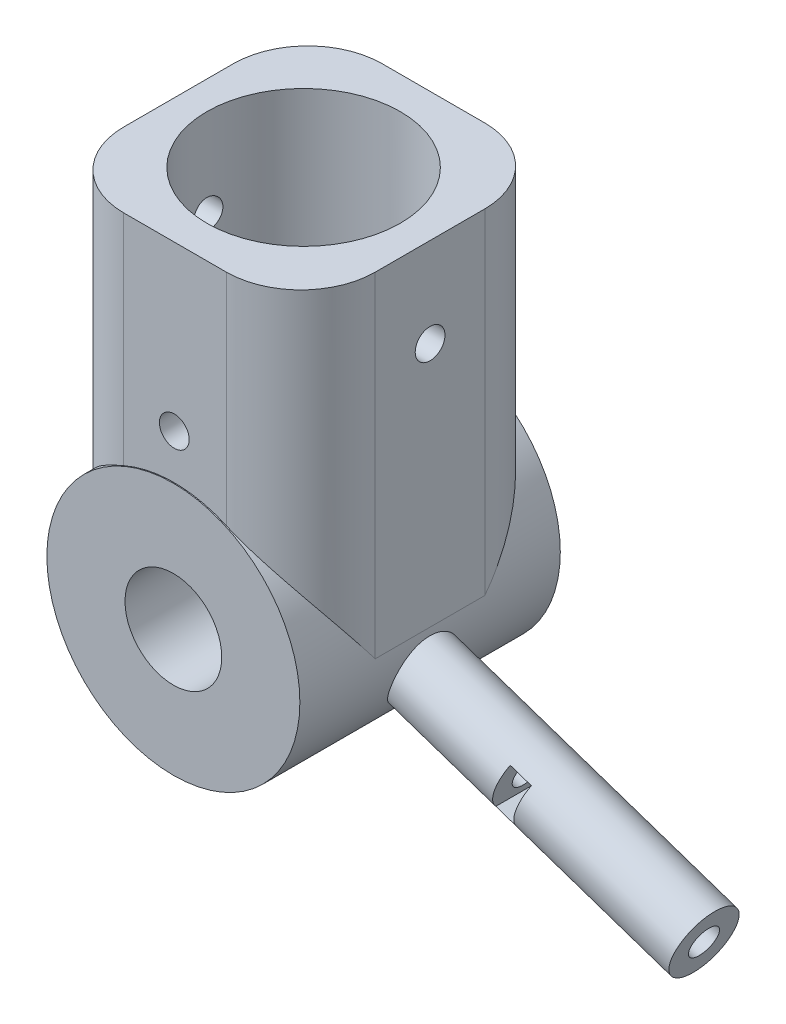
SolidWorks part; units mm, degrees
ref_plane "Спереди" through (0, 0, 0) normal (0, 0, 1) x (1, 0, 0)
ref_plane "Сверху" through (0, 0, 0) normal (0, 1, 0) x (1, 0, 0)
ref_plane "Справа" through (0, 0, 0) normal (1, 0, 0) x (0, 0, -1)
sketch "Эскиз1" plane through (0, 0, 0) normal (0, 0, 1) x (1, 0, 0)
  circle A0 centre (0, 0) radius 6.5
  circle A1 centre (0, 0) radius 17
extrude "Бобышка-Вытянуть2" add sketch "Эскиз1" along normal blind 35
ref_plane "Плоскость4" through (0, 45, 0) normal (0, 1, 0) x (1, 0, 0)
sketch "Эскиз3" plane through (0, 45, 0) normal (0, 1, 0) x (1, 0, 0)
  line L0 (17, -35) -> (17, 0) construction
  line L13 (-16.7953, -0.1471) -> (17, -0.1471)
  line L14 (-16.7953, -0.1471) -> (-16.7953, -34.8751)
  line L15 (-16.7953, -34.8751) -> (17, -34.8751)
  line L16 (17, -0.1471) -> (17, -34.8751)
  line L17 (-16.7953, -0.1471) -> (-17, 0) construction
  line L18 (-17, 0) -> (-17, -35) construction
  line L19 (-16.7953, -34.8751) -> (-17, -35) construction
  circle A1 centre (0, -17.5) radius 13
extrude "Бобышка-Вытянуть7" add sketch "Эскиз3" against normal blind 45
sketch "Эскиз4" plane through (0, 0, 0) normal (0, 0, -1) x (-1, 0, 0)
  circle A0 centre (0, 0) radius 6.5
extrude "Вырез-Вытянуть1" cut sketch "Эскиз4" against normal through all
sketch "Эскиз12" plane through (0, 0, 0) normal (0, 0, -1) x (-1, 0, 0)
  line L0 (0, 23) -> (0, 0) construction
  circle A3 centre (0, 23) radius 2
extrude "Вырез-Вытянуть11" cut sketch "Эскиз12" against normal blind 45
sketch "Эскиз15" plane through (-16.7953, 0, 0) normal (-1, 0, 0) x (0, 0, 1)
  line L0 (0, 0) -> (0, 33) construction
  line L1 (0, 33) -> (17.5, 33) construction
  circle A1 centre (17.5, 33) radius 2
extrude "Вырез-Вытянуть12" cut sketch "Эскиз15" against normal blind 45
fillet "Скругление4" radius 10 4 edges at (-16.7953, 23.8152, 0.1471) (17, 22.5, 0.1471) (17, 22.5, 34.8751) (-16.7953, 23.8152, 34.8751)
sketch "Эскиз20" plane through (0, 45, 0) normal (0, 1, 0) x (1, 0, 0)
  circle A3 centre (0, -17.5) radius 13
extrude "Вырез-Вытянуть18" cut sketch "Эскиз20" against normal blind 31
sketch "Эскиз25" plane through (0, 14, 0) normal (0, 1, 0) x (1, 0, 0)
  circle A2 centre (0, -17.5) radius 13
extrude "Бобышка-Вытянуть10" add sketch "Эскиз25" along normal blind 1
sketch3d "Трехмерный эскиз1"
  point P0 (-14.7779, 8.4033, 37.4657)
sketch "Эскиз26" plane through (0, 0, 0) normal (0, 0, -1) x (-1, 0, 0)
  circle A0 centre (0, 0) radius 6.5
  circle A1 centre (0, 0) radius 5.5
extrude "Бобышка-Вытянуть11" add sketch "Эскиз26" against normal blind 2
sketch3d "Трехмерный эскиз4"
  point P0 (0.8909, -16.9766, 11.3566)
sketch3d "Трехмерный эскиз5"
  point P0 (15.2365, -7.5398, 9.0171)
sketch3d "Трехмерный эскиз6"
  point P0 (16.5585, -3.8494, 24.0123)
sketch3d "Трехмерный эскиз7"
  point P0 (15.9928, -5.7645, 14.4989)
sketch3d "Трехмерный эскиз8"
  point P0 (16.1648, -5.263, 16.1571)
sketch3d "Трехмерный эскиз9"
  point P0 (16.704, -3.1583, 20.9707)
ref_plane "Плоскость12" through (15.9655, -5.3798, 0.0076) normal (0.9476, -0.3193, 0.0005) x (0.0014, 0.0026, -1)
sketch "Эскиз36" plane through (15.9655, -5.3798, 0.0076) normal (0.9476, -0.3193, 0.0005) x (0.0014, 0.0026, -1)
  circle A0 centre (-17.5111, 0) radius 4.5
  circle A1 centre (-17.5111, 0) radius 2
extrude "Бобышка-Вытянуть17" add sketch "Эскиз36" along normal blind 15 and the other way up to body separate body
sketch "Эскиз37" plane through (30.1802, -10.1695, 0.0144) normal (0.9476, -0.3193, 0.0005) x (0.0004, -0.0001, -1)
  line L0 (-19.261, 2.98) -> (-20.8371, 2.98)
  line L7 (-14.011, -0.0511) -> (-15.761, 2.98)
  line L8 (-15.761, 2.98) -> (-19.261, 2.98)
  line L11 (-19.261, -3.0822) -> (-15.761, -3.0822)
  line L12 (-15.761, -3.0822) -> (-14.011, -0.0511)
  line L13 (-19.261, -3.0822) -> (-20.8371, -3.0822)
  line L20 (-19.261, 2.98) -> (-21.011, -0.0511) [skipped]
  line L21 (-21.011, -0.0511) -> (-19.261, -3.0822) [skipped]
  arc A1 (-20.8371, -3.0822) -> (-20.8371, 2.98) centre (-17.511, -0.0511) ccw
  arc A4 (-19.261, -3.0822) -> (-19.261, 2.98) centre (-17.511, -0.0511) ccw construction
extrude "Бобышка-Вытянуть18" add sketch "Эскиз37" along normal blind 3
sketch "Эскиз38" plane through (33.0232, -11.1275, 0.0158) normal (0.9476, -0.3193, 0.0005) x (0.0004, -0.0001, -1)
  circle A0 centre (-17.511, -0.0511) radius 4.5
  circle A1 centre (-17.511, -0.0511) radius 2
extrude "Бобышка-Вытянуть20" add sketch "Эскиз38" along normal blind 22
